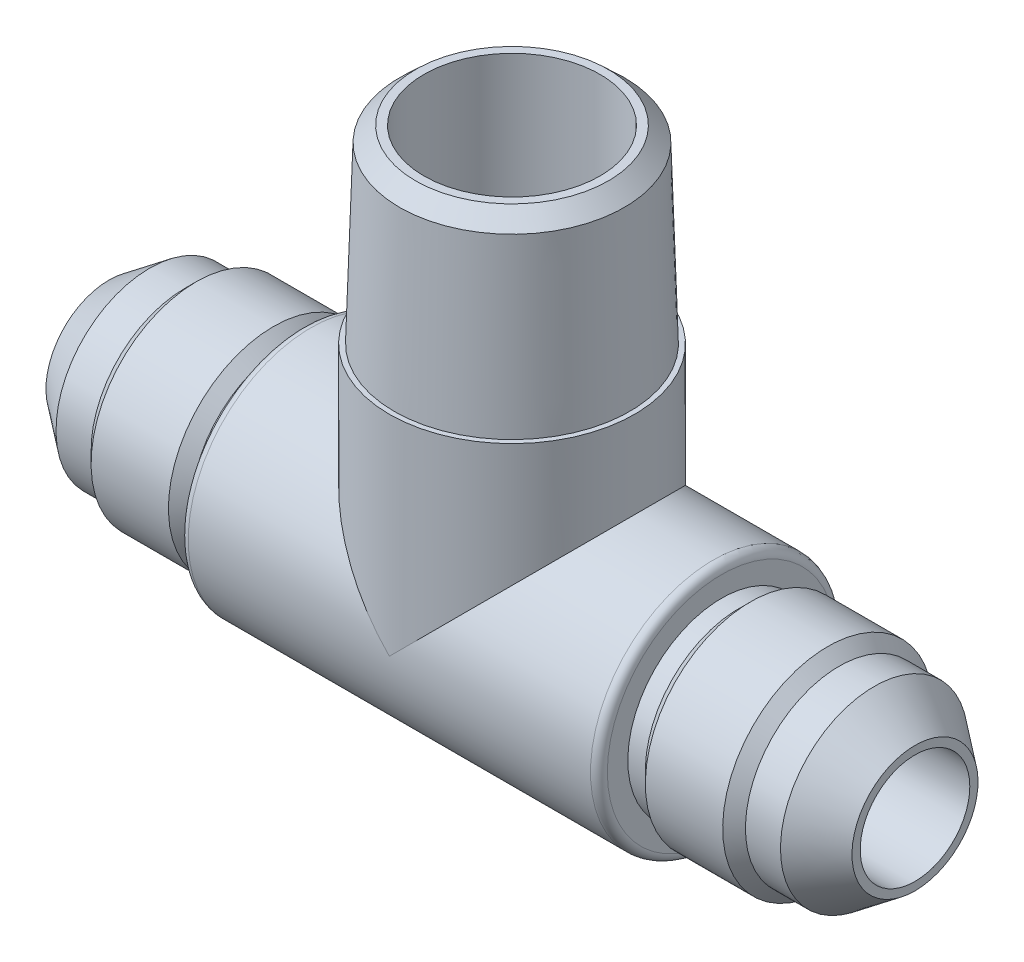
SolidWorks part; units mm, degrees
ref_plane "Front Plane" through (0, 0, 0) normal (0, 0, 1) x (1, 0, 0)
ref_plane "Top Plane" through (0, 0, 0) normal (0, 1, 0) x (1, 0, 0)
ref_plane "Right Plane" through (0, 0, 0) normal (1, 0, 0) x (0, 0, -1)
sketch "Sketch1" plane through (0, 0, 0) normal (0, 0, 1) x (1, 0, 0)
  line L0 (0, 0) -> (-18.9865, 0) construction
  line L1 (0, 0) -> (0, 18.9865) construction
  line L2 (-9.525, 18.9865) -> (9.525, 18.9865) construction
  line L3 (-18.9865, 9.525) -> (-18.9865, -9.525) construction
  line L6 (-36.5125, 9.525) -> (-36.5125, -9.525) construction
  line L8 (-10.668, 36.1163) -> (10.668, 36.1163) construction
  line L9 (0, 0) -> (0, 36.1163) construction
  line L10 (-18.9865, 11.1125) -> (-18.9865, -11.1125) construction
  line L12 (-11.1125, 18.9865) -> (11.1125, 18.9865) construction
  point P15 (0, 22.5603)
  dimension "S" = 17.526
  dimension "Pipe Thread Dia" = 21.336
  dimension "V" = 36.1163
  dimension "TE" = 13.556
  dimension "OA" = 22.225
ref_plane "Plane1" through (-36.5125, 0, 0) normal (1, 0, 0) x (0, 0, -1)
sketch "Sketch2" plane through (-36.5125, 0, 0) normal (1, 0, 0) x (0, 0, -1)
  circle A0 centre (0, 0) radius 9.525
  dimension "Thread OD" = 19.05
extrude "Extrude1" add sketch "Sketch2" along normal up to vertex (17.526 mm away) up to point (-18.9865, 0, 0)
sketch "Sketch3" plane through (-36.5125, 0, 0) normal (-1, 0, 0) x (0, 0, 1)
  circle A0 centre (0, 0) radius 9.525 construction
  circle A1 centre (0, 0) radius 9.525
curve "Helix/Spiral1" pitch 1.5875 height 36.5125 turns 23 parameters "pitch"=1.5875
sketch "Sketch4" plane through (0, 0, 0) normal (0, 0, 1) x (1, 0, 0)
  line L0 (-37.9016, 9.525) -> (-37.3062, 8.4939)
  line L1 (-37.3062, 8.4939) -> (-37.1078, 8.4939)
  line L2 (-37.1078, 8.4939) -> (-36.5125, 9.525)
  line L3 (-37.9016, 9.525) -> (-36.5125, 9.525)
  line L6 (-37.207, 9.525) -> (-37.207, 8.4939) construction
  line L7 (-37.6039, 9.0094) -> (-36.8102, 9.0094) construction
  line L8 (-36.5125, 9.525) -> (-36.5125, -9.525) construction
  dimension "D1" = 0.1984
  dimension "D2" = 0.7937
  dimension "D3" = 60
sweep "Cut-Sweep1" [suppressed] cut profiles "Sketch4" path "Helix/Spiral1"
sketch "Sketch5" plane through (0, 0, 0) normal (0, 0, 1) x (1, 0, 0)
  line L0 (-36.5125, 6.35) -> (-36.5125, -6.35) construction
  line L1 (-32.8189, 8.4939) -> (-29.6439, 8.4939)
  line L2 (-29.6439, 8.4939) -> (-28.6128, 9.525)
  line L3 (-36.5125, 5.7106) -> (-36.5125, -5.7106) construction
  line L4 (-28.6128, 9.525) -> (-36.5125, 9.525)
  line L5 (-37.9016, 9.525) -> (-36.5125, 9.525) construction
  line L6 (-18.9865, 9.525) -> (-18.9865, -9.525) construction
  line L7 (-18.9865, 8.4939) -> (-20.574, 8.4939)
  line L8 (-20.574, 8.4939) -> (-21.6051, 9.525)
  line L9 (-21.6051, 9.525) -> (-18.9865, 9.525)
  line L10 (-18.9865, 8.4939) -> (-18.9865, 9.525)
  line L11 (-27.2626, -9.525) -> (-27.2626, 0) construction
  line L12 (-18.9865, 0) -> (-36.5125, 0) construction
  line L13 (-36.5125, 9.525) -> (-36.5125, -9.525) construction
  line L14 (-36.5125, 5.7106) -> (-32.8189, 8.4939)
  line L15 (-36.5125, 9.525) -> (-36.5125, 5.7106)
  line L16 (0, 0) -> (-18.9865, 0) construction
  point P16 (-27.2626, -9.525)
  dimension "D3" = 45
  dimension "D5" = 45
  dimension "D6" = 1.5875
  dimension "Tube OD" = 12.7
  dimension "D2" = 11.4211
  dimension "D1" = 37
  dimension "D4" = 3.175
  dimension "D7" = 2.3813
revolve "Cut-Revolve1" cut sketch "Sketch5" angle 360 about L0
ref_plane "Plane2" through (-18.9865, 0, 0) normal (1, 0, 0) x (0, 0, -1)
sketch "Sketch15" plane through (-18.9865, 0, 0) normal (1, 0, 0) x (0, 0, -1)
  circle A0 centre (0, 0) radius 11.1125
extrude "Boss-Extrude1" add sketch "Sketch15" along normal up to vertex (18.9865 mm away) up to point (0, 0, 0)
sketch "Sketch16" plane through (0, 0, 0) normal (1, 0, 0) x (0, 0, -1)
  circle A0 centre (0, 0) radius 4.9657
  dimension "Min ID" = 9.9314
extrude "Cut-Extrude1" cut sketch "Sketch16" against normal through all
ref_plane "Plane3" through (0, 18.9865, 0) normal (0, 1, 0) x (-1, 0, 0)
sketch "Sketch20" plane through (0, 18.9865, 0) normal (0, 1, 0) x (-1, 0, 0)
  circle A0 centre (0, 0) radius 11.1125
extrude "Boss-Extrude2" add sketch "Sketch20" against normal up to vertex (18.9865 mm away) separate body up to point (0, 0, 0)
sketch "Sketch22" plane through (0, 18.9865, 0) normal (0, 1, 0) x (-1, 0, 0)
  circle A0 centre (0, 0) radius 10.668
extrude "Boss-Extrude3" add sketch "Sketch22" along normal up to vertex (17.1298 mm away) draft 1.75 separate body up to point (0, 36.1163, 0)
sketch "Sketch23" plane through (0, 36.1163, 0) normal (0, 1, 0) x (1, 0, 0)
  circle A0 centre (0, 0) radius 10.1446 construction
  circle A1 centre (0, 0) radius 10.1446
curve "Helix/Spiral2" parameters "Pitch"=1.8143
chamfer "Chamfer1" distance 1.3607 angle 45 1 edges at (0, 36.1163, 10.1446) first distance on face at (0, 36.1163, 10.1446)
sketch "Sketch25" plane through (0, 18.9865, 0) normal (0, -1, 0) x (1, 0, 0)
  circle A1 centre (0, 0) radius 10.668
  circle A2 centre (0, 0) radius 10.668
  dimension "D1" = 0
sketch "Sketch24" plane through (0, 0, 0) normal (0, 0, 1) x (1, 0, 0)
  line L0 (10.2428, 37.8738) -> (10.2428, 36.0596) construction
  line L1 (10.2428, 36.0596) -> (8.6716, 36.9667) construction
  line L2 (8.6716, 36.9667) -> (10.2428, 37.8738) construction
  line L3 (8.868, 37.0801) -> (8.868, 36.8533)
  line L4 (8.6716, 36.9667) -> (8.868, 36.9667) construction
  line L5 (10.0464, 37.7605) -> (10.0464, 36.173) construction
  line L6 (10.0464, 36.9667) -> (10.2428, 36.9667) construction
  line L7 (10.1446, 36.9667) -> (10.1446, 36.1163) construction
  line L8 (10.1446, 37.8172) -> (10.2428, 36.0596)
  line L9 (10.2428, 36.0596) -> (8.868, 36.8533)
  line L10 (8.868, 37.0801) -> (10.1446, 37.8172)
  dimension "D1" = 1.8143
  dimension "D2" = 0.2268
sweep "Cut-Sweep2" [suppressed] cut profiles "Sketch24" path "Helix/Spiral2"
extrude "Boss-Extrude4" add sketch "Sketch25" against normal up to vertex (17.1298 mm away) draft 15 up to point (10.668, 36.1163, 0)
sketch "Sketch28" plane through (0, 36.1163, 0) normal (0, 1, 0) x (1, 0, 0)
  circle A2 centre (0, 0) radius 7.9784
  circle A3 centre (0, 0) radius 7.9784
  dimension "D1" = 0.762
extrude "Cut-Extrude6" cut sketch "Sketch28" against normal up to vertex (17.1298 mm away) up to point (0, 18.9865, 0)
fillet "Fillet1" radius 0.762 1 edges at (-18.9865, 0, -11.1125)
sketch "Sketch10" plane through (0, 0, 0) normal (1, 0, 0) x (0, 0, -1)
  line L0 (0, 0) -> (-12.651, 0) construction
ref_axis "Axis1" through (0, 0, 12.651) along (0, 0, -1)
pattern_circular "CirPattern1" count 2 over 180 about axis through (0, 0, 12.651) along (0, 0, -1) reverse direction yes of bodies 110 103
combine bodies "Combine2" operation type add bodies to combine 110 122 114 105
sketch "Sketch30" plane through (0, 0, 0) normal (0, 0, 1) x (1, 0, 0)
  line L0 (0, 18.9865) -> (0, 9.4932)
  line L1 (0, 18.9865) -> (-10.922, 18.9865)
  line L2 (0, 0) -> (0, 18.9865) construction
  line L3 (-10.922, 18.9865) -> (0, 9.4932) construction
  line L4 (-5.461, 14.2399) -> (-6.1275, 13.4731) construction
  line L5 (-10.922, 18.9865) -> (-10.922, 18.4785)
  arc A0 (-10.922, 18.4785) -> (0, 9.4932) centre (13.649, 37.215) ccw
  point P2 (0, 9.4932)
  dimension "D1" = 0.254
  dimension "D2" = 1.016
  dimension "D3" = 0.508
revolve "Revolve1" add sketch "Sketch30" angle 360 about L0
sketch "Sketch26" plane through (-36.5125, 0, 0) normal (-1, 0, 0) x (0, 0, 1)
  circle A0 centre (0, 0) radius 4.9657 construction
  circle A1 centre (0, 0) radius 4.9657
extrude "Cut-Extrude4" cut sketch "Sketch26" against normal through all
sketch "Sketch29" plane through (0, 0, 0) normal (0, 1, 0) x (1, 0, 0)
  circle A0 centre (0, 0) radius 4.9657
  dimension "D1" = 9.9314
extrude "Cut-Extrude7" cut sketch "Sketch29" along normal through all
sketch "Sketch12" plane through (0, 0, 0) normal (0, 0, 1) x (1, 0, 0)
  line L0 (0, 0) -> (0, 36.1163) construction
  line L2 (0, 0) -> (-36.5125, 0) construction
  line L3 (7.9784, 36.1163) -> (-7.9784, 36.1163) construction
sketch "Sketch13" plane through (0, 0, 0) normal (1, 0, 0) x (0, 0, -1)
  line L0 (9.525, 18.9865) -> (-9.525, 18.9865)
  line L1 (0, 0) -> (0, 18.9865) construction
  line L3 (9.525, 0) -> (-9.525, 0)
  circle A0 centre (0, 0) radius 4.9657
  circle A1 centre (0, 0) radius 4.9657 construction
  dimension "D1" = 19.05
sketch "Sketch31" [suppressed] plane through (-36.5125, 0, 0) normal (-1, 0, 0) x (0, 0, 1)
  point P0 (0, 0)
sketch "Sketch32" [suppressed] plane through (36.5125, 0, 0) normal (1, 0, 0) x (0, 0, -1)
  point P0 (0, 0)
other "CPoint1" parameters "Diameter"=12.7, "StubLength"=28.575
ref_axis "Axis2" through (-46.5125, 0, 0) along (1, 0, 0)
other "CPoint2" parameters "Diameter"=12.7, "StubLength"=19.05
ref_axis "Axis3" through (46.5125, 0, 0) along (-1, 0, 0)
equation "\"D1@Sketch1\" = \"Thread OD@Sketch2\""
equation "\"D3@Helix/Spiral1\" = \"Q@Sketch1\""
equation "\"D1@Sketch4\" = \"pitch@Helix/Spiral1\"*.125"
equation "\"D2@Sketch4\" = \"pitch@Helix/Spiral1\"*.5"
equation "\"D6@Sketch5\" = \"pitch@Helix/Spiral1\"*1"
equation "\"D4@Sketch5\" = \"pitch@Helix/Spiral1\"*2"
equation "\"D1@Sketch13\" = \"D1@Sketch1\""
equation "\"D7@Sketch5\" = \"pitch@Helix/Spiral1\"*1.5"
equation "\"D2@Sketch5\" = \"Min ID@Sketch16\"*1.15"
equation "\"D1@Sketch24\" = \"Pitch@Helix/Spiral2\""
equation "\"D2@Sketch24\" = \"Pitch@Helix/Spiral2\"/8"
equation "\"D1@Chamfer1\" = \"Pitch@Helix/Spiral2\"*.750"
equation "\"D1@Sketch29\" =  \"Min ID@Sketch16\""
